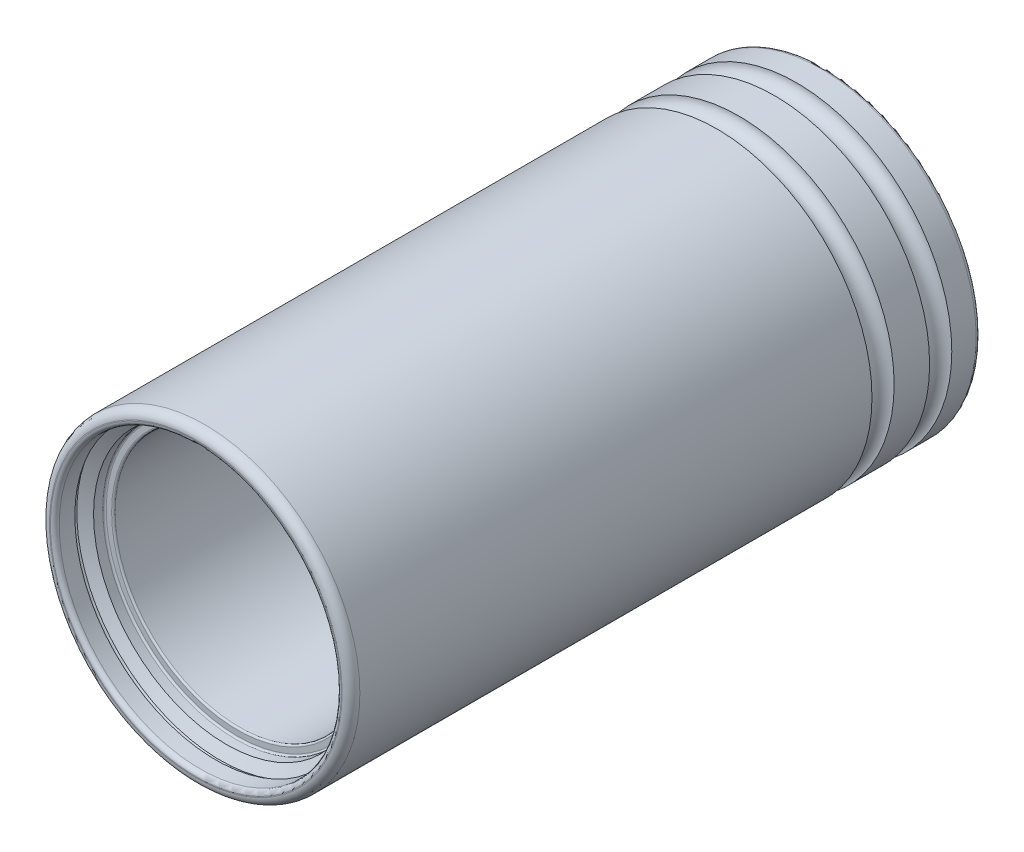
SolidWorks part; units mm, degrees
material "AISI 304"
ref_plane "Спереди" through (0, 0, 0) normal (0, 0, 1) x (1, 0, 0)
ref_plane "Сверху" through (0, 0, 0) normal (0, 1, 0) x (1, 0, 0)
ref_plane "Справа" through (0, 0, 0) normal (1, 0, 0) x (0, 0, -1)
sketch "Эскиз1" plane through (0, 0, 0) normal (0, 0, 1) x (1, 0, 0)
  circle A0 centre (0, 0) radius 17.5
  dimension "D1" = 35
extrude "Бобышка-Вытянуть1" add sketch "Эскиз1" against normal blind 71
sketch "Эскиз4" plane through (0, 0, 0) normal (1, 0, 0) x (0, 0, -1)
  line L0 (0, 0) -> (0, 15)
  line L1 (0, 17.5) -> (0, -17.5) construction
  line L2 (0, 15) -> (4.7, 15)
  line L3 (4.7, 15) -> (4.7, 14)
  line L4 (4.7, 14) -> (23.5, 14)
  line L5 (23.5, 14) -> (23.5, 11)
  line L6 (23.5, 11) -> (29.3001, 9.5)
  line L7 (29.3001, 9.5) -> (29.3536, 9.5)
  line L8 (29.3536, 9.5) -> (29.3536, 10.1)
  line L9 (29.3536, 10.1) -> (30.5536, 10.1)
  line L10 (30.5536, 10.1) -> (30.9, 9.5)
  line L11 (30.9, 9.5) -> (45, 9.5)
  line L12 (45, 9.5) -> (45, 7.5)
  line L13 (45, 7.5) -> (45.5236, 5.5)
  line L14 (45.5236, 5.5) -> (48, 5.5)
  line L15 (48, 5.5) -> (48, 9.5)
  line L16 (48, 9.5) -> (51.8, 9.5)
  line L20 (53, 9.5) -> (54.5, 9.5)
  line L21 (54.5, 9.5) -> (54.5, 10.75)
  line L22 (54.5, 10.75) -> (66, 10.75)
  line L23 (66, 10.75) -> (66, 12.4)
  line L24 (66, 12.4) -> (69, 12.4)
  line L25 (69, 12.4) -> (69, 10.75)
  line L26 (69, 10.75) -> (71, 10.75)
  line L27 (71, -17.5) -> (71, 17.5) construction
  line L28 (71, 10.75) -> (71, 0)
  line L29 (71, 0) -> (0, 0)
  line L30 (0, 50) -> (0, -50) construction
  arc A0 (51.8, 9.5) -> (53, 9.5) centre (52.4, 9.5) cw
  dimension "D8" = 0.6
  dimension "D1" = 10.75
  dimension "D2" = 12.4
  dimension "D3" = 2
  dimension "D4" = 3
  dimension "D5" = 16.5
  dimension "D6" = 2.1
  dimension "D7" = 9.5
  dimension "D9" = 14.1
  dimension "D10" = 75.329
  dimension "D11" = 14.5
  dimension "D12" = 15
  dimension "D13" = 14
  dimension "D14" = 4.7
  dimension "D15" = 23.5
  dimension "D16" = 60
  dimension "D17" = 11
  dimension "D18" = 5.5
  dimension "D19" = 1.2
  dimension "D20" = 23
  dimension "D22" = 45
  dimension "D23" = 7.5
revolve "Вырез-Повернуть1" cut sketch "Эскиз4" angle 360 about L29
sketch "Эскиз5" plane through (0, 0, 0) normal (1, 0, 0) x (0, 0, -1)
  line L0 (3.466, 15) -> (1.734, 15)
  line L1 (1.734, 15) -> (2.6, 16.5)
  line L2 (2.6, 16.5) -> (3.466, 15)
  line L3 (4.7, 15) -> (4.7, -15) construction
  line L4 (4.7, 15) -> (4.7, -15) construction
  line L5 (0, 15) -> (0, -15) construction
  line L6 (0, 0) -> (8.2655, 0) construction
  line L7 (0, 17.5) -> (0, -17.5) construction
  line L8 (0, 17.5) -> (0, -17.5) construction
  point P3 (2.6, 15)
  dimension "D1" = 1
  dimension "D2" = 60
  dimension "D3" = 2.6
revolve "Вырез-Повернуть2" cut sketch "Эскиз5" angle 360 about L6
fillet "Скругление1" radius 0.2 2 edges at (16.5, 0, -2.6) (-15, 0, -4.7)
fillet "Скругление2" radius 1 2 edges at (-14, 0, -23.5) (17.5, 0, 0)
sketch "Эскиз6" plane through (0, 0, 0) normal (0, 0, 1) x (1, 0, 0)
  circle A0 centre (0, 0) radius 14 construction
  circle A1 centre (0, 0) radius 14
  circle A2 centre (0, 0) radius 15.9
  dimension "D1" = 31.8
extrude "Вырез-Вытянуть1" cut sketch "Эскиз6" against normal blind 2.6
fillet "Скругление3" radius 0.5 6 edges at (-10.75, 0, -71) (17.5, 0, -71) (-5.5, 0, -48) (-5.5, 0, -45.5236) (-9.5, 0, -29.3001) (-11, 0, -23.5)
fillet "Скругление4" radius 0.1 2 edges at (-10.1, 0, -30.5536) (-10.1, 0, -29.3536)
fillet "Скругление5" radius 0.2 3 edges at (-10.75, 0, -69) (-10.75, 0, -66) (-9.5, 0, -30.9)
fillet "Скругление6" radius 0.4 2 edges at (-12.4, 0, -69) (-12.4, 0, -66)
fillet "Скругление7" radius 0.2 3 edges at (-10.75, 0, -54.5) (-9.5, 0, -54.5) (-14, 0, -4.7)
sketch "Эскиз7" plane through (0, 0, 0) normal (0, 1, 0) x (1, 0, 0)
  line L0 (17, 71) -> (-17, 71) construction
  line L1 (-15.75, 71) -> (-13.25, 71)
  line L2 (0, 88.9589) -> (0, 57.4428) construction
  arc A0 (-15.75, 71) -> (-13.25, 71) centre (-14.5, 71) cw
  dimension "D1" = 1.25
  dimension "D2" = 14.5
revolve "Повернуть1" add sketch "Эскиз7" angle 360 about L2
sketch "Эскиз8" plane through (0, 0, 0) normal (1, 0, 0) x (0, 0, -1)
  line L0 (1, -17.5) -> (1, 17.5) construction
  line L1 (1, -17.5) -> (1, 17.5) construction
  line L2 (66.5, 17.5) -> (40.6285, 17.5) construction
  line L7 (0, 0) -> (74.6339, 0) construction
  line L8 (71, -17) -> (71, 17) construction
  line L9 (71, -17) -> (71, 17) construction
  line L10 (70.5, 17.5) -> (1, 17.5) construction
  circle A0 centre (66.5, 17.5) radius 1.25
  circle A1 centre (60, 17.5) radius 1.25
  dimension "D1" = 2.5
  dimension "D3" = 2.5
  dimension "D4" = 6.5
  dimension "D2" = 4.5
revolve "Вырез-Повернуть3" cut sketch "Эскиз8" angle 360 about L7
fillet "Скругление10" radius 0.2 1 edges at (-9.5, 0, -48)
fillet "Скругление11" radius 0.5 1 edges at (15.9, 0, 0)
ref_plane "Плоскость1" through (0, 0, -60) normal (0, 0, 1) x (1, 0, 0)
ref_plane "Плоскость2" through (0, 0, -66.5) normal (0, 0, 1) x (1, 0, 0)
ref_plane "Плоскость3" through (0, 0, -67.5) normal (0, 0, 1) x (1, 0, 0)
